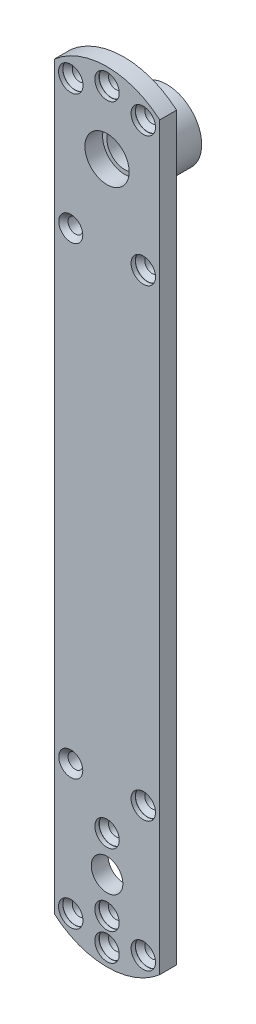
SolidWorks part; units mm, degrees
ref_plane "Front Plane" through (0, 0, 0) normal (0, 0, 1) x (1, 0, 0)
ref_plane "Top Plane" through (0, 0, 0) normal (0, 1, 0) x (1, 0, 0)
ref_plane "Right Plane" through (0, 0, 0) normal (1, 0, 0) x (0, 0, -1)
sketch "Sketch1" plane through (0, 0, 0) normal (0, 0, 1) x (1, 0, 0)
  line L0 (18.375, 147) -> (18.375, 0)
  line L1 (43.375, 147) -> (43.375, 0)
  circle A0 centre (30.875, 8.5) radius 1.75
  circle A1 centre (30.875, 0) radius 12.5 construction
  circle A2 centre (30.875, 0) radius 12.5
  circle A3 centre (30.875, -8.5) radius 1.75
  circle A4 centre (30.875, 0) radius 3.75
  circle A5 centre (30.875, -8.5) radius 1.25 construction
  circle A6 centre (30.875, 147) radius 12.5
  circle A7 centre (30.875, 147) radius 5.25
  circle A8 centre (30.875, 147) radius 5 construction
  circle A11 centre (30.875, 8.5) radius 1.25 construction
  circle A12 centre (30.875, 147) radius 5 construction
  dimension "D2" = 3.5
  dimension "D3" = 7.5
  dimension "D1" = 0.25
extrude "Boss-Extrude1" add sketch "Sketch1" along normal blind 4 contours A6 | A6 L0 A2 L1 | A2 A4 A3 A0 region at (30.875, 73.5, 0) region at (30.875, 159.1464, 0) region at (30.875, 12.1464, 0)
sketch "Sketch2" plane through (0, 0, 0) normal (0, 0, 1) x (1, 0, 0)
  circle A0 centre (30.875, 147) radius 5.25
  circle A1 centre (30.875, 147) radius 5.25 construction
  circle A2 centre (30.875, 147) radius 8.25
  dimension "D1" = 3
extrude "Boss-Extrude2" add sketch "Sketch2" against normal blind 0.2
sketch "Sketch3" plane through (0, 0, -0.2) normal (0, 0, -1) x (-1, 0, 0)
  circle A0 centre (-30.875, 147) radius 8.25 construction
  circle A1 centre (-30.875, 147) radius 8.25
  circle A2 centre (-30.875, 147) radius 4.25
  circle A3 centre (-30.875, 147) radius 5.25 construction
  dimension "D1" = 1
extrude "Boss-Extrude3" add sketch "Sketch3" along normal blind 5.8
sketch "Sketch4" plane through (0, 0, -6) normal (0, 0, -1) x (-1, 0, 0)
  circle A0 centre (-30.875, 147) radius 8.25 construction
  circle A1 centre (-30.875, 147) radius 8.25
  circle A2 centre (-30.875, 147) radius 5.25
  circle A3 centre (-30.875, 147) radius 5.25 construction
extrude "Boss-Extrude4" add sketch "Sketch4" along normal blind 4.2
sketch "Sketch9" plane through (0, 0, 0) normal (0, 0, -1) x (-1, 0, 0)
  line L0 (-43.375, 161.3091) -> (-43.375, -14.3091)
  line L1 (-43.375, 147) -> (-43.375, 0) construction
  line L2 (-18.375, 161.3091) -> (-18.375, -14.3091)
  line L3 (-18.375, 147) -> (-18.375, 0) construction
  circle A0 centre (-30.875, 147) radius 19
  circle A1 centre (-30.875, 0) radius 19
  arc A2 (-18.375, 147) -> (-43.375, 147) centre (-30.875, 147) ccw construction
  arc M15 (-18.375, 147) -> (-43.375, 147) centre (-30.875, 147) ccw
  arc M17 (-43.375, 0) -> (-18.375, 0) centre (-30.875, 0) ccw
  dimension "D1" = 6.5
extrude "Boss-Extrude5" add sketch "Sketch9" against normal up to surface (4 mm away) contours L2 A0 L0 M15 | L0 A1 L2 M17 region at (30.875, 160.2864, 0) region at (30.875, -13.2864, 0) up to face at (36.125, 147, 4)
sketch "Sketch10" plane through (0, 0, 4) normal (0, 0, 1) x (1, 0, 0)
  line L0 (30.875, 166) -> (30.875, -19) construction
  line L1 (30.875, 147) -> (19.977, 162.5639) construction
  line L2 (39.4786, 159.2873) -> (39.4786, -12.2873) construction
  line L3 (18.375, 73.5) -> (43.375, 73.5) construction
  line L4 (18.375, 161.3091) -> (18.375, -14.3091) construction
  line L5 (43.375, 161.3091) -> (43.375, -14.3091) construction
  circle A0 centre (30.875, 147) radius 15
  arc A1 (43.375, 161.3091) -> (18.375, 161.3091) centre (30.875, 147) ccw construction
  arc A2 (18.375, -14.3091) -> (43.375, -14.3091) centre (30.875, 0) ccw construction
  circle A3 centre (30.875, 162) radius 1.75
  circle A4 centre (22.2714, 159.2873) radius 1.75
  circle A5 centre (39.4786, 159.2873) radius 1.75
  circle A6 centre (39.4786, -12.2873) radius 1.75
  circle A7 centre (30.875, -15) radius 1.75
  circle A8 centre (22.2714, -12.2873) radius 1.75
  circle A9 centre (39.4786, 128.5) radius 1.75
  circle A10 centre (39.4786, 18.5) radius 1.75
  circle A11 centre (22.2714, 18.5) radius 1.75
  circle A12 centre (22.2714, 128.5) radius 1.75
  dimension "D1" = 4
  dimension "D2" = 3.5
  dimension "D3" = 35
  dimension "D4" = 110
extrude "Cut-Extrude4" cut sketch "Sketch10" against normal up to next contours A0 A4 | A0 A4 | A0 A3 | A0 A3 | A5 A0 | A5 A0 | A8 | A7 | A6 | A9 | A10 | A12 | A11 region at (39.0423, 158.6641, 4) region at (39.8939, 159.8804, 4) region at (21.8561, 159.8804, 4) region at (22.7077, 158.6641, 4) region at (30.875, 161.2392, 4) region at (30.875, 162.724, 4) region at (39.4786, -12.2873, 4) region at (30.875, -15, 4) region at (22.2714, -12.2873, 4) region at (39.4786, 128.5, 4) region at (39.4786, 18.5, 4) region at (22.2714, 18.5, 4) region at (22.2714, 128.5, 4)
sketch "Sketch8" plane through (0, 0, 4) normal (0, 0, 1) x (1, 0, 0)
  circle A0 centre (30.875, 8.5) radius 2.9
  circle A1 centre (30.875, -8.5) radius 2.9
  circle A2 centre (22.2714, -12.2873) radius 2.9
  circle A3 centre (30.875, -15) radius 2.9
  circle A4 centre (39.4786, -12.2873) radius 2.9
  circle A5 centre (22.2714, 159.2873) radius 2.9
  circle A6 centre (30.875, 162) radius 2.9
  circle A7 centre (39.4786, 159.2873) radius 2.9
  circle A8 centre (39.4786, 159.2873) radius 1.75 construction
  circle A9 centre (39.4786, -12.2873) radius 1.75 construction
  circle A10 centre (22.2714, -12.2873) radius 1.75 construction
  circle A11 centre (30.875, -15) radius 1.75 construction
  circle A12 centre (39.4786, 128.5) radius 2.9
  circle A13 centre (39.4786, 18.5) radius 2.9
  circle M10 centre (30.875, -8.5) radius 1.75
  circle M11 centre (30.875, 8.5) radius 1.75
  circle M59 centre (39.4786, 18.5) radius 1.75
  circle M60 centre (39.4786, 128.5) radius 1.75
  dimension "D1" = 5.8
extrude "Cut-Extrude3" cut sketch "Sketch8" against normal blind 1 contours A5 | A6 | A7 | A2 | A3 | A4 | A0 M11 | A1 M10 | A12 M60 | A13 M59 region at (28.057, 8.5, 4) region at (28.057, -8.5, 4) region at (22.2714, -12.2873, 4) region at (30.875, -15, 4) region at (39.4786, -12.2873, 4) region at (22.2714, 159.2873, 4) region at (30.875, 162, 4) region at (39.4786, 159.2873, 4) region at (36.6607, 128.5, 4) region at (36.6607, 18.5, 4)
chamfer "Chamfer1" distance 1.1 angle 45 12 edges at (41.2286, -12.2873, 3) (32.625, -15, 3) (24.0214, -12.2873, 3) (41.2286, 159.2873, 3) (32.625, 162, 3) (24.0214, 159.2873, 3) (32.625, -8.5, 3) (32.625, 8.5, 3) (41.2286, 18.5, 3) (41.2286, 128.5, 3) (24.0214, 128.5, 4) (24.0214, 18.5, 4)
fillet "Fillet2" radius 2 1 edges at (39.125, 147, 0)
sketch "Sketch11" plane through (0, 0, 0) normal (0, 0, 1) x (1, 0, 0)
  line L0 (43.375, 161.3091) -> (43.375, -14.3091) construction
  line L1 (25.375, 28.5) -> (42.375, 28.5)
  line L2 (25.375, 28.5) -> (25.375, 118.5)
  line L3 (25.375, 118.5) -> (42.375, 118.5)
  line L4 (42.375, 28.5) -> (42.375, 118.5)
  line L5 (18.375, 73.5) -> (43.375, 73.5) construction
  line L6 (18.375, 161.3091) -> (18.375, -14.3091) construction
  line L7 (25.375, 73.5) -> (42.375, 73.5) construction
  dimension "D1" = 1
  dimension "D2" = 90
  dimension "D3" = 17
extrude "Cut-Extrude5" cut sketch "Sketch11" along normal offset from surface (3 mm away) 1 up to face at (25.1214, 128.5, 4)
